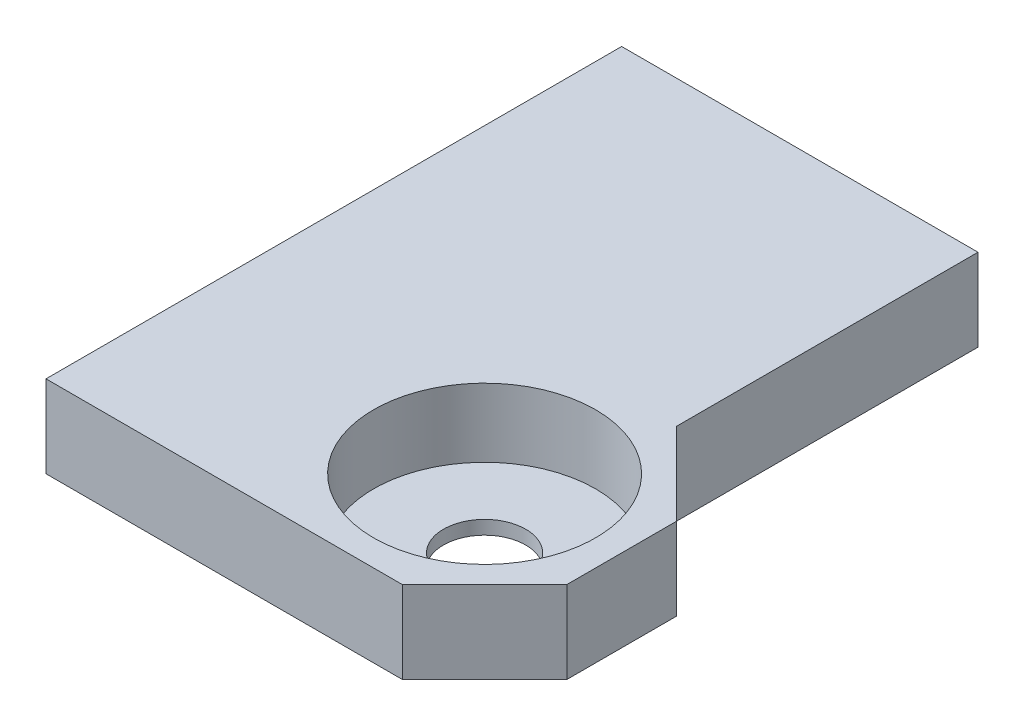
SolidWorks part; units mm, degrees
ref_plane "Front Plane" through (0, 0, 0) normal (0, 0, 1) x (1, 0, 0)
ref_plane "Top Plane" through (0, 0, 0) normal (0, 1, 0) x (1, 0, 0)
ref_plane "Right Plane" through (0, 0, 0) normal (1, 0, 0) x (0, 0, -1)
sketch "Sketch1" plane through (0, 0, 0) normal (0, 1, 0) x (1, 0, 0)
  line L0 (0, 0) -> (32, 0)
  line L1 (32, 0) -> (32, 20)
  line L2 (32, 20) -> (26, 20)
  line L3 (26, 20) -> (26, 42)
  line L4 (26, 42) -> (0, 42)
  line L5 (0, 42) -> (0, 0)
  circle A0 centre (22, 10) radius 3
  point P9 (0, 41.1919)
  point P10 (20.4518, 42.3099)
  point P11 (32.7495, 19.0954)
  point P12 (42.5483, 20)
  dimension "D1" = 6
  dimension "D2" = 10
  dimension "D3" = 10
  dimension "D4" = 10
  dimension "D5" = 42
  dimension "D6" = 6
  dimension "D7" = 26
extrude "Boss-Extrude1" add sketch "Sketch1" along normal blind 6
chamfer "Chamfer1" distance 6 angle 45 2 edges at (32, 3, -20) (32, 3, 0)
sketch "Sketch2" plane through (0, 6, 0) normal (0, 1, 0) x (1, 0, 0)
  circle A0 centre (22, 10) radius 8.1
  dimension "D3" = 16.2
  dimension "D1" = 22
  dimension "D2" = 10
extrude "Cut-Extrude1" cut sketch "Sketch2" against normal blind 5
sketch "Sketch3" plane through (0, 6, 0) normal (0, 1, 0) x (1, 0, 0)
  circle A0 centre (6.1454, 50) radius 6.349
  circle A1 centre (22, 10) radius 3 construction
  dimension "D1" = 40
